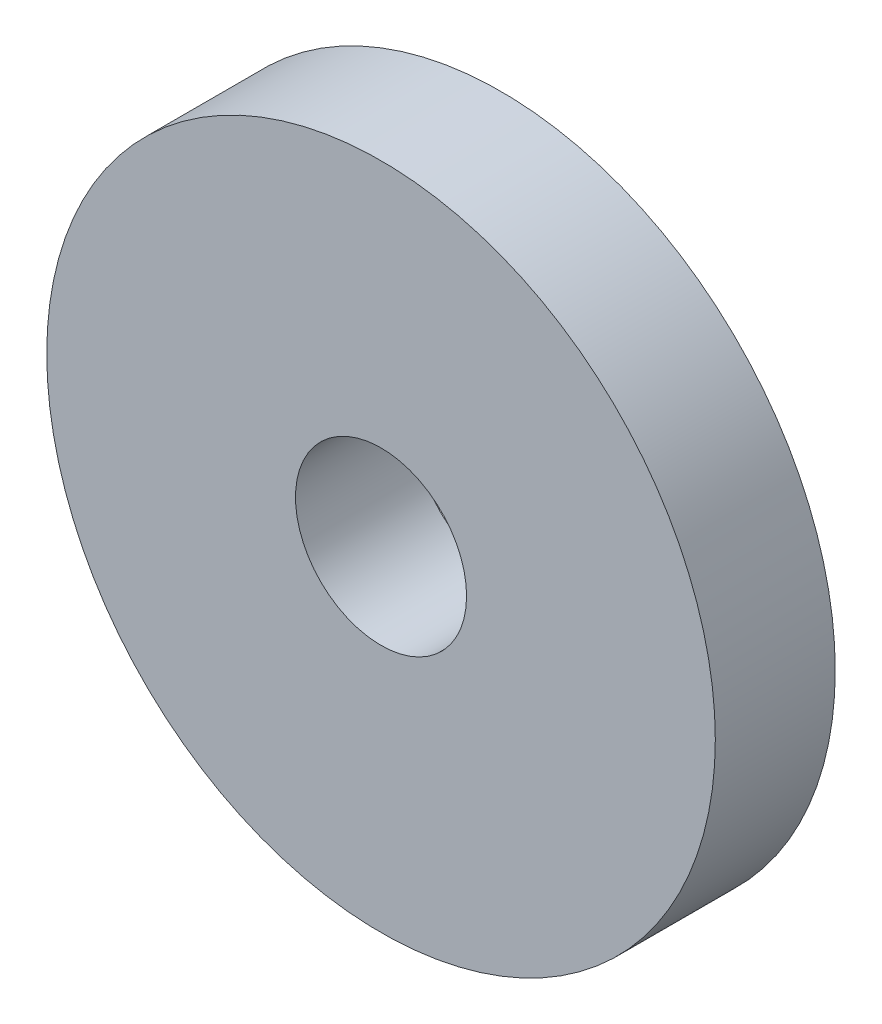
SolidWorks part; units mm, degrees
material "Brass"
ref_plane "Front Plane" through (0, 0, 0) normal (0, 0, 1) x (1, 0, 0)
ref_plane "Top Plane" through (0, 0, 0) normal (0, 1, 0) x (1, 0, 0)
ref_plane "Right Plane" through (0, 0, 0) normal (1, 0, 0) x (0, 0, -1)
sketch "Sketch1" plane through (0, 0, 0) normal (0, 0, 1) x (1, 0, 0)
  circle A0 centre (0, 0) radius 12.7
  circle A1 centre (0, 0) radius 3.25
  dimension "D1" = 25.4
  dimension "D2" = 6.5
extrude "Boss-Extrude1" add sketch "Sketch1" along normal mid plane 4.5565
